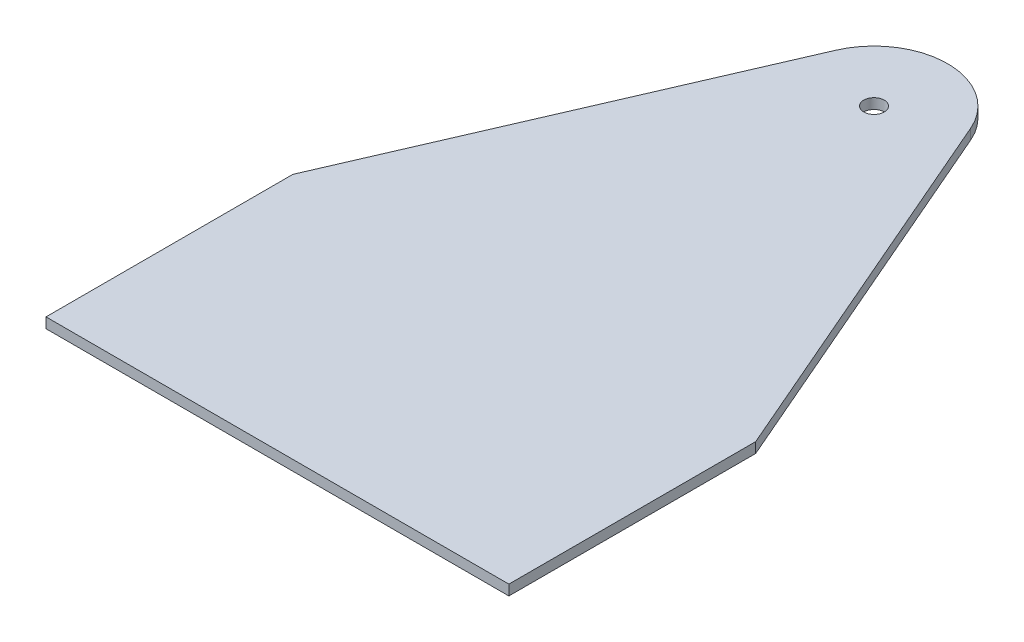
SolidWorks part; units mm, degrees
ref_plane "Front Plane" through (0, 0, 0) normal (0, 0, 1) x (1, 0, 0)
ref_plane "Top Plane" through (0, 0, 0) normal (0, 1, 0) x (1, 0, 0)
ref_plane "Right Plane" through (0, 0, 0) normal (1, 0, 0) x (0, 0, -1)
sketch "Sketch1" plane through (0, 0, 0) normal (0, 1, 0) x (1, 0, 0)
  line L0 (-71.4375, 0) -> (71.4375, 0)
  line L1 (-71.4375, 19.05) -> (71.4375, 19.05) construction
  line L2 (-71.4375, 0) -> (-71.4375, 76.2)
  line L3 (-71.4375, 19.05) -> (0, 184.15) construction
  line L8 (0, 184.15) -> (71.4375, 19.05) construction
  line L13 (71.4375, 0) -> (71.4375, 76.2)
  line L14 (-71.4375, 76.2) -> (-20.8288, 193.1624)
  line L15 (20.8288, 193.1624) -> (71.4375, 76.2)
  arc A0 (-20.8288, 193.1624) -> (20.8288, 193.1624) centre (0, 184.15) cw
  circle A1 centre (0, 184.15) radius 3.175
  point P4 (0, 0)
  dimension "D5" = 6.35
  dimension "D1" = 142.875
  dimension "D2" = 165.1
  dimension "D3" = 19.05
  dimension "D4" = 76.2
extrude "Boss-Extrude1" add sketch "Sketch1" along normal blind 3.175
